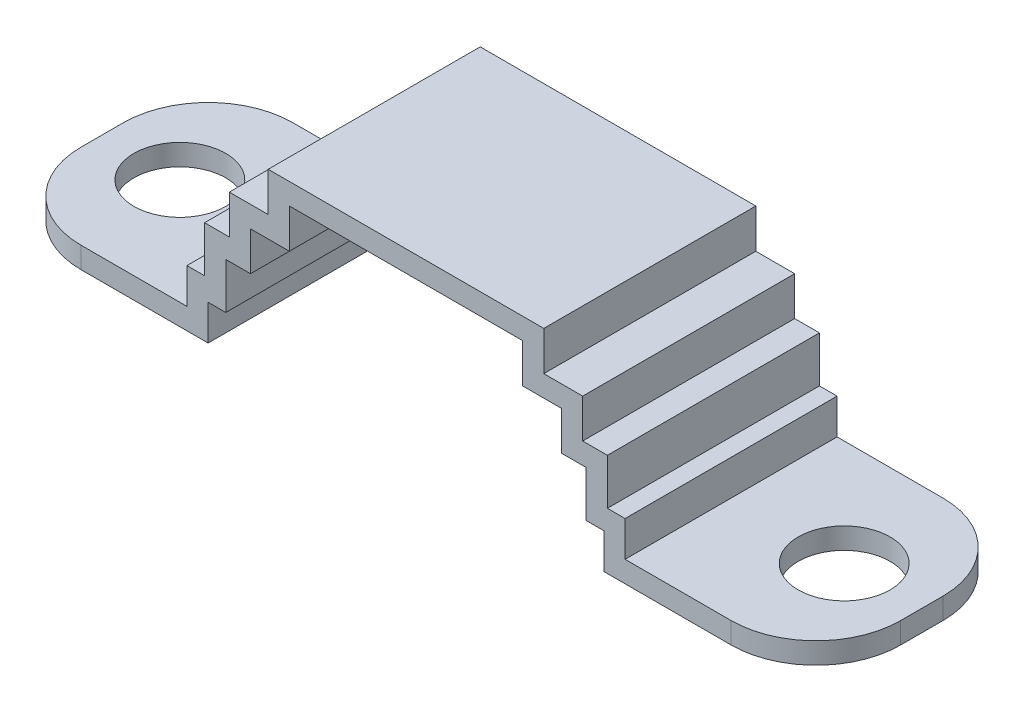
SolidWorks part; units mm, degrees
material "PBT General Purpose"
ref_plane "Front Plane" through (0, 0, 0) normal (0, 0, 1) x (1, 0, 0)
ref_plane "Top Plane" through (0, 0, 0) normal (0, 1, 0) x (1, 0, 0)
ref_plane "Right Plane" through (0, 0, 0) normal (1, 0, 0) x (0, 0, -1)
sketch "Sketch1" plane through (0, 0, 0) normal (0, 0, 1) x (1, 0, 0)
  line L0 (-58, 4.5) -> (-28, 4.5)
  line L1 (-28, 4.5) -> (-28, 9.5)
  line L2 (-28, 9.5) -> (-25.5, 9.5)
  line L3 (-25.5, 9.5) -> (-25.5, 16)
  line L4 (-25.5, 16) -> (-22, 16)
  line L5 (-22, 16) -> (-22, 21.5)
  line L6 (-22, 21.5) -> (-16.5, 21.5)
  line L7 (-16.5, 21.5) -> (-16.5, 27.05)
  line L8 (-16.5, 27.05) -> (0, 27.05)
  circle A0 centre (0, 0) radius 27.05
  dimension "D1" = 54.1
  dimension "D2" = 30
  dimension "D3" = 4.5
  dimension "D4" = 28
  dimension "D5" = 5
  dimension "D6" = 2.5
  dimension "D7" = 6.5
  dimension "D8" = 3.5
  dimension "D9" = 5.5
  dimension "D10" = 5.5
  dimension "D11" = 16.5
  dimension "D12" = 5.55
extrude "Extrude-Thin1" add sketch "Sketch1" along normal mid plane 30 thin contours L0 L1 L2 L3 L4 L5 L6 L7 L8 thin type one direction reverse wall 3
sketch "Sketch2" plane through (0, 7.5, 0) normal (0, 1, 0) x (1, 0, 0)
  line L0 (0, -15) -> (0, 15) construction
  circle A0 centre (-47, 0) radius 6.5
  dimension "D1" = 13
  dimension "D2" = 47
extrude "Cut-Extrude1" cut sketch "Sketch2" against normal through all
fillet "Fillet1" radius 12 2 edges at (-58, 6, -15) (-58, 6, 15)
mirror "Mirror1" about plane through (0, 30.05, 15) normal (1, 0, 0) of "Fillet1", "Cut-Extrude1", "Extrude-Thin1"
